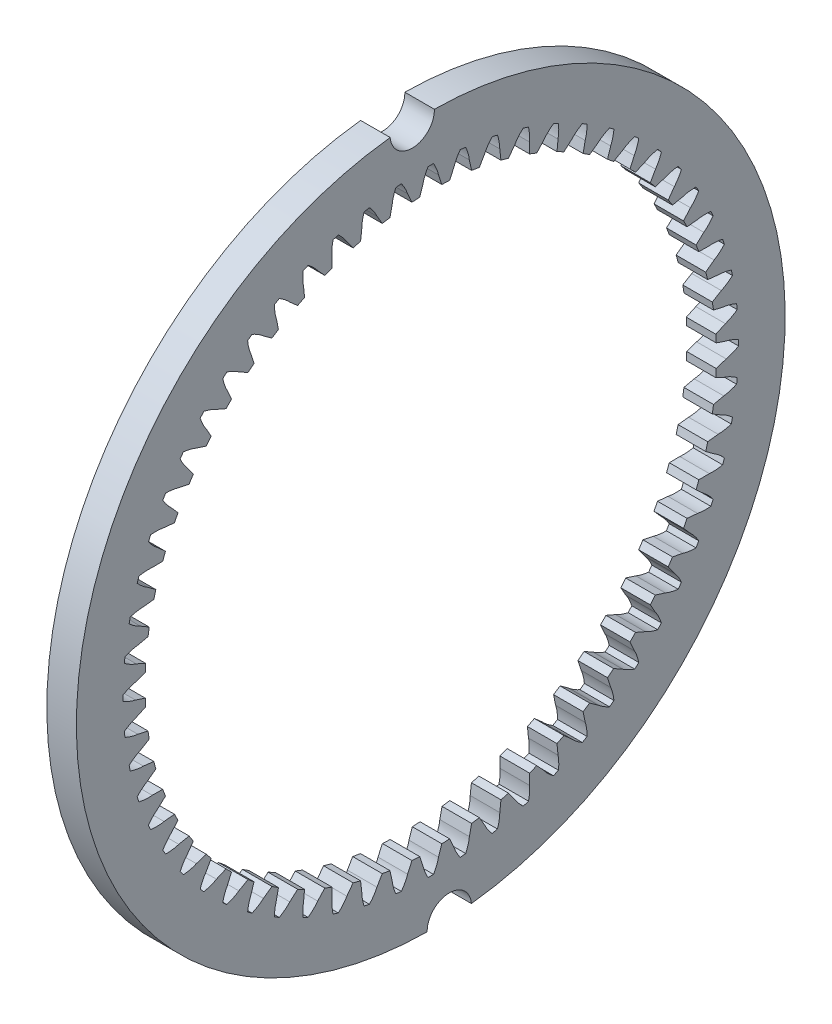
SolidWorks part; units mm, degrees
ref_plane "Front Plane" through (0, 0, 0) normal (0, 0, 1) x (1, 0, 0)
ref_plane "Top Plane" through (0, 0, 0) normal (0, 1, 0) x (1, 0, 0)
ref_plane "Right Plane" through (0, 0, 0) normal (1, 0, 0) x (0, 0, -1)
ref_plane "Plane1" through (1.5875, 0, 0) normal (1, 0, 0) x (0, 0, -1)
sketch "Sketch1" plane through (1.5875, 0, 0) normal (1, 0, 0) x (0, 0, -1)
  line L0 (4.1442, 31.4784) -> (4.3886, 30.3763)
  line L1 (5.2129, 30.2457) -> (5.786, 31.2183)
  line L2 (7.4119, 30.8727) -> (7.5398, 29.7511)
  line L3 (8.3459, 29.5351) -> (9.0175, 30.4425)
  line L4 (10.5984, 29.9289) -> (10.6083, 28.8)
  line L5 (11.3875, 28.5009) -> (12.1502, 29.3332)
  line L6 (13.6687, 28.6571) -> (13.5606, 27.5334)
  line L7 (14.3042, 27.1545) -> (15.1498, 27.9024)
  line L8 (16.5893, 27.0713) -> (16.3644, 25.9651)
  line L9 (17.0643, 25.5105) -> (17.9834, 26.166)
  line L10 (19.3282, 25.189) -> (18.9888, 24.1123)
  line L11 (19.6374, 23.5871) -> (20.62, 24.1429)
  line L12 (21.8553, 23.0306) -> (21.4052, 21.9953)
  line L13 (21.9953, 21.4052) -> (23.0306, 21.8553)
  line L14 (24.1429, 20.62) -> (23.5871, 19.6374)
  line L15 (24.1123, 18.9888) -> (25.189, 19.3282)
  line L16 (26.166, 17.9834) -> (25.5105, 17.0643)
  line L17 (25.9651, 16.3644) -> (27.0713, 16.5893)
  line L18 (27.9024, 15.1498) -> (27.1545, 14.3042)
  line L19 (27.5334, 13.5606) -> (28.6571, 13.6687)
  line L20 (29.3332, 12.1502) -> (28.5009, 11.3875)
  line L21 (28.8, 10.6083) -> (29.9289, 10.5984)
  line L22 (30.4425, 9.0175) -> (29.5351, 8.3459)
  line L23 (29.7511, 7.5398) -> (30.8727, 7.4119)
  line L24 (31.2183, 5.786) -> (30.2457, 5.2129)
  line L25 (30.3763, 4.3886) -> (31.4784, 4.1442)
  line L26 (31.6521, 2.4911) -> (30.6249, 2.0228)
  line L27 (30.6686, 1.1894) -> (31.7391, 0.8311)
  line L28 (31.7391, -0.8311) -> (30.6686, -1.1894)
  line L29 (30.6249, -2.0228) -> (31.6521, -2.4911)
  line L30 (31.4784, -4.1442) -> (30.3763, -4.3886)
  line L31 (30.2457, -5.2129) -> (31.2183, -5.786)
  line L32 (30.8727, -7.4119) -> (29.7511, -7.5398)
  line L33 (29.5351, -8.3459) -> (30.4425, -9.0175)
  line L34 (29.9289, -10.5984) -> (28.8, -10.6083)
  line L35 (28.5009, -11.3875) -> (29.3332, -12.1502)
  line L36 (28.6571, -13.6687) -> (27.5334, -13.5606)
  line L37 (27.1545, -14.3042) -> (27.9024, -15.1498)
  line L38 (27.0713, -16.5893) -> (25.9651, -16.3644)
  line L39 (25.5105, -17.0643) -> (26.166, -17.9834)
  line L40 (25.189, -19.3282) -> (24.1123, -18.9888)
  line L41 (23.5871, -19.6374) -> (24.1429, -20.62)
  line L42 (23.0306, -21.8553) -> (21.9953, -21.4052)
  line L43 (21.4052, -21.9953) -> (21.8553, -23.0306)
  line L44 (20.62, -24.1429) -> (19.6374, -23.5871)
  line L45 (18.9888, -24.1123) -> (19.3282, -25.189)
  line L46 (17.9834, -26.166) -> (17.0643, -25.5105)
  line L47 (16.3644, -25.9651) -> (16.5893, -27.0713)
  line L48 (15.1498, -27.9024) -> (14.3042, -27.1545)
  line L49 (13.5606, -27.5334) -> (13.6687, -28.6571)
  line L50 (12.1502, -29.3332) -> (11.3875, -28.5009)
  line L51 (10.6083, -28.8) -> (10.5984, -29.9289)
  line L52 (9.0175, -30.4425) -> (8.3459, -29.5351)
  line L53 (7.5398, -29.7511) -> (7.4119, -30.8727)
  line L54 (5.786, -31.2183) -> (5.2129, -30.2457)
  line L55 (4.3886, -30.3763) -> (4.1442, -31.4784)
  line L56 (2.4911, -31.6521) -> (2.0228, -30.6249)
  line L57 (1.1894, -30.6686) -> (0.8311, -31.7391)
  line L58 (-0.8311, -31.7391) -> (-1.1894, -30.6686)
  line L59 (-2.0228, -30.6249) -> (-2.4911, -31.6521)
  line L60 (-4.1442, -31.4784) -> (-4.3886, -30.3763)
  line L61 (-5.2129, -30.2457) -> (-5.786, -31.2183)
  line L62 (-7.4119, -30.8727) -> (-7.5398, -29.7511)
  line L63 (-8.3459, -29.5351) -> (-9.0175, -30.4425)
  line L64 (-10.5984, -29.9289) -> (-10.6083, -28.8)
  line L65 (-11.3875, -28.5009) -> (-12.1502, -29.3332)
  line L66 (-13.6687, -28.6571) -> (-13.5606, -27.5334)
  line L67 (-14.3042, -27.1545) -> (-15.1498, -27.9024)
  line L68 (-16.5893, -27.0713) -> (-16.3644, -25.9651)
  line L69 (-17.0643, -25.5105) -> (-17.9834, -26.166)
  line L70 (-19.3282, -25.189) -> (-18.9888, -24.1123)
  line L71 (-19.6374, -23.5871) -> (-20.62, -24.1429)
  line L72 (-21.8553, -23.0306) -> (-21.4052, -21.9953)
  line L73 (-21.9953, -21.4052) -> (-23.0306, -21.8553)
  line L74 (-24.1429, -20.62) -> (-23.5871, -19.6374)
  line L75 (-24.1123, -18.9888) -> (-25.189, -19.3282)
  line L76 (-26.166, -17.9834) -> (-25.5105, -17.0643)
  line L77 (-25.9651, -16.3644) -> (-27.0713, -16.5893)
  line L78 (-27.9024, -15.1498) -> (-27.1545, -14.3042)
  line L79 (-27.5334, -13.5606) -> (-28.6571, -13.6687)
  line L80 (-29.3332, -12.1502) -> (-28.5009, -11.3875)
  line L81 (-28.8, -10.6083) -> (-29.9289, -10.5984)
  line L82 (-30.4425, -9.0175) -> (-29.5351, -8.3459)
  line L83 (-29.7511, -7.5398) -> (-30.8727, -7.4119)
  line L84 (-31.2183, -5.786) -> (-30.2457, -5.2129)
  line L85 (-30.3763, -4.3886) -> (-31.4784, -4.1442)
  line L86 (-31.6521, -2.4911) -> (-30.6249, -2.0228)
  line L87 (-30.6686, -1.1894) -> (-31.7391, -0.8311)
  line L88 (-31.7391, 0.8311) -> (-30.6686, 1.1894)
  line L89 (-30.6249, 2.0228) -> (-31.6521, 2.4911)
  line L90 (-31.4784, 4.1442) -> (-30.3763, 4.3886)
  line L91 (-30.2457, 5.2129) -> (-31.2183, 5.786)
  line L92 (-30.8727, 7.4119) -> (-29.7511, 7.5398)
  line L93 (-29.5351, 8.3459) -> (-30.4425, 9.0175)
  line L94 (-29.9289, 10.5984) -> (-28.8, 10.6083)
  line L95 (-28.5009, 11.3875) -> (-29.3332, 12.1502)
  line L96 (-28.6571, 13.6687) -> (-27.5334, 13.5606)
  line L97 (-27.1545, 14.3042) -> (-27.9024, 15.1498)
  line L98 (-27.0713, 16.5893) -> (-25.9651, 16.3644)
  line L99 (-25.5105, 17.0643) -> (-26.166, 17.9834)
  line L100 (-25.189, 19.3282) -> (-24.1123, 18.9888)
  line L101 (-23.5871, 19.6374) -> (-24.1429, 20.62)
  line L102 (-23.0306, 21.8553) -> (-21.9953, 21.4052)
  line L103 (-21.4052, 21.9953) -> (-21.8553, 23.0306)
  line L104 (-20.62, 24.1429) -> (-19.6374, 23.5871)
  line L105 (-18.9888, 24.1123) -> (-19.3282, 25.189)
  line L106 (-17.9834, 26.166) -> (-17.0643, 25.5105)
  line L107 (-16.3644, 25.9651) -> (-16.5893, 27.0713)
  line L108 (-15.1498, 27.9024) -> (-14.3042, 27.1545)
  line L109 (-13.5606, 27.5334) -> (-13.6687, 28.6571)
  line L110 (-12.1502, 29.3332) -> (-11.3875, 28.5009)
  line L111 (-10.6083, 28.8) -> (-10.5984, 29.9289)
  line L112 (-9.0175, 30.4425) -> (-8.3459, 29.5351)
  line L113 (-7.5398, 29.7511) -> (-7.4119, 30.8727)
  line L114 (-5.786, 31.2183) -> (-5.2129, 30.2457)
  line L115 (-4.3886, 30.3763) -> (-4.1442, 31.4784)
  line L116 (-2.4911, 31.6521) -> (-2.0228, 30.6249)
  line L117 (-1.1894, 30.6686) -> (-0.8311, 31.7391)
  line L118 (0.8311, 31.7391) -> (1.1894, 30.6686)
  line L119 (2.0228, 30.6249) -> (2.4911, 31.6521)
  arc A0 (3.1625, 32.9192) -> (3.7509, 32.8574) centre (0, 0) cw
  arc A1 (4.3886, 30.3763) -> (5.2129, 30.2457) centre (0, 0) cw
  arc A2 (6.5862, 32.4083) -> (7.1649, 32.2853) centre (0, 0) cw
  arc A3 (7.5398, 29.7511) -> (8.3459, 29.5351) centre (0, 0) cw
  arc A4 (9.9377, 31.5423) -> (10.5003, 31.3595) centre (0, 0) cw
  arc A5 (10.6083, 28.8) -> (11.3875, 28.5009) centre (0, 0) cw
  arc A6 (13.1804, 30.3308) -> (13.7208, 30.0902) centre (0, 0) cw
  arc A7 (13.5606, 27.5334) -> (14.3042, 27.1545) centre (0, 0) cw
  arc A8 (16.2786, 28.7869) -> (16.7909, 28.4911) centre (0, 0) cw
  arc A9 (16.3644, 25.9651) -> (17.0643, 25.5105) centre (0, 0) cw
  arc A10 (19.1985, 26.9276) -> (19.677, 26.5799) centre (0, 0) cw
  arc A11 (18.9888, 24.1123) -> (19.6374, 23.5871) centre (0, 0) cw
  arc A12 (21.908, 24.7733) -> (22.3476, 24.3775) centre (0, 0) cw
  arc A13 (21.4052, 21.9953) -> (21.9953, 21.4052) centre (0, 0) cw
  arc A14 (24.3775, 22.3476) -> (24.7733, 21.908) centre (0, 0) cw
  arc A15 (23.5871, 19.6374) -> (24.1123, 18.9888) centre (0, 0) cw
  arc A16 (26.5799, 19.677) -> (26.9276, 19.1985) centre (0, 0) cw
  arc A17 (25.5105, 17.0643) -> (25.9651, 16.3644) centre (0, 0) cw
  arc A18 (28.4911, 16.7909) -> (28.7869, 16.2786) centre (0, 0) cw
  arc A19 (27.1545, 14.3042) -> (27.5334, 13.5606) centre (0, 0) cw
  arc A20 (30.0902, 13.7208) -> (30.3308, 13.1804) centre (0, 0) cw
  arc A21 (28.5009, 11.3875) -> (28.8, 10.6083) centre (0, 0) cw
  arc A22 (31.3595, 10.5003) -> (31.5423, 9.9377) centre (0, 0) cw
  arc A23 (29.5351, 8.3459) -> (29.7511, 7.5398) centre (0, 0) cw
  arc A24 (32.2853, 7.1649) -> (32.4083, 6.5862) centre (0, 0) cw
  arc A25 (30.2457, 5.2129) -> (30.3763, 4.3886) centre (0, 0) cw
  arc A26 (32.8574, 3.7509) -> (32.9192, 3.1625) centre (0, 0) cw
  arc A27 (30.6249, 2.0228) -> (30.6686, 1.1894) centre (0, 0) cw
  arc A28 (33.0695, 0.2958) -> (33.0695, -0.2958) centre (0, 0) cw
  arc A29 (30.6686, -1.1894) -> (30.6249, -2.0228) centre (0, 0) cw
  arc A30 (32.9192, -3.1625) -> (32.8574, -3.7509) centre (0, 0) cw
  arc A31 (30.3763, -4.3886) -> (30.2457, -5.2129) centre (0, 0) cw
  arc A32 (32.4083, -6.5862) -> (32.2853, -7.1649) centre (0, 0) cw
  arc A33 (29.7511, -7.5398) -> (29.5351, -8.3459) centre (0, 0) cw
  arc A34 (31.5423, -9.9377) -> (31.3595, -10.5003) centre (0, 0) cw
  arc A35 (28.8, -10.6083) -> (28.5009, -11.3875) centre (0, 0) cw
  arc A36 (30.3308, -13.1804) -> (30.0902, -13.7208) centre (0, 0) cw
  arc A37 (27.5334, -13.5606) -> (27.1545, -14.3042) centre (0, 0) cw
  arc A38 (28.7869, -16.2786) -> (28.4911, -16.7909) centre (0, 0) cw
  arc A39 (25.9651, -16.3644) -> (25.5105, -17.0643) centre (0, 0) cw
  arc A40 (26.9276, -19.1985) -> (26.5799, -19.677) centre (0, 0) cw
  arc A41 (24.1123, -18.9888) -> (23.5871, -19.6374) centre (0, 0) cw
  arc A42 (24.7733, -21.908) -> (24.3775, -22.3476) centre (0, 0) cw
  arc A43 (21.9953, -21.4052) -> (21.4052, -21.9953) centre (0, 0) cw
  arc A44 (22.3476, -24.3775) -> (21.908, -24.7733) centre (0, 0) cw
  arc A45 (19.6374, -23.5871) -> (18.9888, -24.1123) centre (0, 0) cw
  arc A46 (19.677, -26.5799) -> (19.1985, -26.9276) centre (0, 0) cw
  arc A47 (17.0643, -25.5105) -> (16.3644, -25.9651) centre (0, 0) cw
  arc A48 (16.7909, -28.4911) -> (16.2786, -28.7869) centre (0, 0) cw
  arc A49 (14.3042, -27.1545) -> (13.5606, -27.5334) centre (0, 0) cw
  arc A50 (13.7208, -30.0902) -> (13.1804, -30.3308) centre (0, 0) cw
  arc A51 (11.3875, -28.5009) -> (10.6083, -28.8) centre (0, 0) cw
  arc A52 (10.5003, -31.3595) -> (9.9377, -31.5423) centre (0, 0) cw
  arc A53 (8.3459, -29.5351) -> (7.5398, -29.7511) centre (0, 0) cw
  arc A54 (7.1649, -32.2853) -> (6.5862, -32.4083) centre (0, 0) cw
  arc A55 (5.2129, -30.2457) -> (4.3886, -30.3763) centre (0, 0) cw
  arc A56 (3.7509, -32.8574) -> (3.1625, -32.9192) centre (0, 0) cw
  arc A57 (2.0228, -30.6249) -> (1.1894, -30.6686) centre (0, 0) cw
  arc A58 (0.2958, -33.0695) -> (-0.2958, -33.0695) centre (0, 0) cw
  arc A59 (-1.1894, -30.6686) -> (-2.0228, -30.6249) centre (0, 0) cw
  arc A60 (-3.1625, -32.9192) -> (-3.7509, -32.8574) centre (0, 0) cw
  arc A61 (-4.3886, -30.3763) -> (-5.2129, -30.2457) centre (0, 0) cw
  arc A62 (-6.5862, -32.4083) -> (-7.1649, -32.2853) centre (0, 0) cw
  arc A63 (-7.5398, -29.7511) -> (-8.3459, -29.5351) centre (0, 0) cw
  arc A64 (-9.9377, -31.5423) -> (-10.5003, -31.3595) centre (0, 0) cw
  arc A65 (-10.6083, -28.8) -> (-11.3875, -28.5009) centre (0, 0) cw
  arc A66 (-13.1804, -30.3308) -> (-13.7208, -30.0902) centre (0, 0) cw
  arc A67 (-13.5606, -27.5334) -> (-14.3042, -27.1545) centre (0, 0) cw
  arc A68 (-16.2786, -28.7869) -> (-16.7909, -28.4911) centre (0, 0) cw
  arc A69 (-16.3644, -25.9651) -> (-17.0643, -25.5105) centre (0, 0) cw
  arc A70 (-19.1985, -26.9276) -> (-19.677, -26.5799) centre (0, 0) cw
  arc A71 (-18.9888, -24.1123) -> (-19.6374, -23.5871) centre (0, 0) cw
  arc A72 (-21.908, -24.7733) -> (-22.3476, -24.3775) centre (0, 0) cw
  arc A73 (-21.4052, -21.9953) -> (-21.9953, -21.4052) centre (0, 0) cw
  arc A74 (-24.3775, -22.3476) -> (-24.7733, -21.908) centre (0, 0) cw
  arc A75 (-23.5871, -19.6374) -> (-24.1123, -18.9888) centre (0, 0) cw
  arc A76 (-26.5799, -19.677) -> (-26.9276, -19.1985) centre (0, 0) cw
  arc A77 (-25.5105, -17.0643) -> (-25.9651, -16.3644) centre (0, 0) cw
  arc A78 (-28.4911, -16.7909) -> (-28.7869, -16.2786) centre (0, 0) cw
  arc A79 (-27.1545, -14.3042) -> (-27.5334, -13.5606) centre (0, 0) cw
  arc A80 (-30.0902, -13.7208) -> (-30.3308, -13.1804) centre (0, 0) cw
  arc A81 (-28.5009, -11.3875) -> (-28.8, -10.6083) centre (0, 0) cw
  arc A82 (-31.3595, -10.5003) -> (-31.5423, -9.9377) centre (0, 0) cw
  arc A83 (-29.5351, -8.3459) -> (-29.7511, -7.5398) centre (0, 0) cw
  arc A84 (-32.2853, -7.1649) -> (-32.4083, -6.5862) centre (0, 0) cw
  arc A85 (-30.2457, -5.2129) -> (-30.3763, -4.3886) centre (0, 0) cw
  arc A86 (-32.8574, -3.7509) -> (-32.9192, -3.1625) centre (0, 0) cw
  arc A87 (-30.6249, -2.0228) -> (-30.6686, -1.1894) centre (0, 0) cw
  arc A88 (-33.0695, -0.2958) -> (-33.0695, 0.2958) centre (0, 0) cw
  arc A89 (-30.6686, 1.1894) -> (-30.6249, 2.0228) centre (0, 0) cw
  arc A90 (-32.9192, 3.1625) -> (-32.8574, 3.7509) centre (0, 0) cw
  arc A91 (-30.3763, 4.3886) -> (-30.2457, 5.2129) centre (0, 0) cw
  arc A92 (-32.4083, 6.5862) -> (-32.2853, 7.1649) centre (0, 0) cw
  arc A93 (-29.7511, 7.5398) -> (-29.5351, 8.3459) centre (0, 0) cw
  arc A94 (-31.5423, 9.9377) -> (-31.3595, 10.5003) centre (0, 0) cw
  arc A95 (-28.8, 10.6083) -> (-28.5009, 11.3875) centre (0, 0) cw
  arc A96 (-30.3308, 13.1804) -> (-30.0902, 13.7208) centre (0, 0) cw
  arc A97 (-27.5334, 13.5606) -> (-27.1545, 14.3042) centre (0, 0) cw
  arc A98 (-28.7869, 16.2786) -> (-28.4911, 16.7909) centre (0, 0) cw
  arc A99 (-25.9651, 16.3644) -> (-25.5105, 17.0643) centre (0, 0) cw
  arc A100 (-26.9276, 19.1985) -> (-26.5799, 19.677) centre (0, 0) cw
  arc A101 (-24.1123, 18.9888) -> (-23.5871, 19.6374) centre (0, 0) cw
  arc A102 (-24.7733, 21.908) -> (-24.3775, 22.3476) centre (0, 0) cw
  arc A103 (-21.9953, 21.4052) -> (-21.4052, 21.9953) centre (0, 0) cw
  arc A104 (-22.3476, 24.3775) -> (-21.908, 24.7733) centre (0, 0) cw
  arc A105 (-19.6374, 23.5871) -> (-18.9888, 24.1123) centre (0, 0) cw
  arc A106 (-19.677, 26.5799) -> (-19.1985, 26.9276) centre (0, 0) cw
  arc A107 (-17.0643, 25.5105) -> (-16.3644, 25.9651) centre (0, 0) cw
  arc A108 (-16.7909, 28.4911) -> (-16.2786, 28.7869) centre (0, 0) cw
  arc A109 (-14.3042, 27.1545) -> (-13.5606, 27.5334) centre (0, 0) cw
  arc A110 (-13.7208, 30.0902) -> (-13.1804, 30.3308) centre (0, 0) cw
  arc A111 (-11.3875, 28.5009) -> (-10.6083, 28.8) centre (0, 0) cw
  arc A112 (-10.5003, 31.3595) -> (-9.9377, 31.5423) centre (0, 0) cw
  arc A113 (-8.3459, 29.5351) -> (-7.5398, 29.7511) centre (0, 0) cw
  arc A114 (-7.1649, 32.2853) -> (-6.5862, 32.4083) centre (0, 0) cw
  arc A115 (-5.2129, 30.2457) -> (-4.3886, 30.3763) centre (0, 0) cw
  arc A116 (-3.7509, 32.8574) -> (-3.1625, 32.9192) centre (0, 0) cw
  arc A117 (-2.0228, 30.6249) -> (-1.1894, 30.6686) centre (0, 0) cw
  arc A118 (-0.2958, 33.0695) -> (0.2958, 33.0695) centre (0, 0) cw
  arc A119 (1.1894, 30.6686) -> (2.0228, 30.6249) centre (0, 0) cw
  circle A120 centre (0, 0) radius 38.0746
  spline S0 degree 3 poles (2.4911, 31.6521) (2.5346, 31.7951) (2.5901, 31.9347) (2.6528, 32.0704) (2.7217, 32.2196) (2.8, 32.3646) (2.885, 32.5053) (2.9709, 32.6475) (3.064, 32.7855) (3.1625, 32.9192) knots 0 0 0 0 0.000448 0.000448 0.000448 0.000941 0.000941 0.000941 0.001439 0.001439 0.001439 0.001439
  spline S1 degree 3 poles (3.7509, 32.8574) (3.8086, 32.7255) (3.8619, 32.5916) (3.9099, 32.4559) (3.9579, 32.3202) (4.0007, 32.1825) (4.0371, 32.0432) (4.0856, 31.8578) (4.1233, 31.6689) (4.1442, 31.4784) knots 0 0 0 0 0.000432 0.000432 0.000432 0.000864 0.000864 0.000864 0.00144 0.00144 0.00144 0.00144
  spline S2 degree 3 poles (5.786, 31.2183) (5.8442, 31.356) (5.914, 31.489) (5.9905, 31.6174) (6.0747, 31.7586) (6.1677, 31.8947) (6.2669, 32.0256) (6.3673, 32.1581) (6.4742, 32.2856) (6.5862, 32.4083) knots 0 0 0 0 0.000448 0.000448 0.000448 0.000941 0.000941 0.000941 0.001439 0.001439 0.001439 0.001439
  spline S3 degree 3 poles (7.1649, 32.2853) (7.2085, 32.1482) (7.2475, 32.0094) (7.281, 31.8694) (7.3145, 31.7294) (7.3427, 31.588) (7.3644, 31.4457) (7.3933, 31.2562) (7.411, 31.0644) (7.4119, 30.8727) knots 0 0 0 0 0.000432 0.000432 0.000432 0.000864 0.000864 0.000864 0.00144 0.00144 0.00144 0.00144
  spline S4 degree 3 poles (9.0175, 30.4425) (9.0898, 30.5734) (9.1731, 30.6983) (9.2626, 30.818) (9.3611, 30.9496) (9.4678, 31.0752) (9.5802, 31.1951) (9.6938, 31.3163) (9.8135, 31.432) (9.9377, 31.5423) knots 0 0 0 0 0.000448 0.000448 0.000448 0.000941 0.000941 0.000941 0.001439 0.001439 0.001439 0.001439
  spline S5 degree 3 poles (10.5003, 31.3595) (10.5294, 31.2186) (10.5537, 31.0765) (10.5724, 30.9338) (10.5911, 30.791) (10.6044, 30.6474) (10.6111, 30.5036) (10.62, 30.3122) (10.6175, 30.1195) (10.5984, 29.9289) knots 0 0 0 0 0.000432 0.000432 0.000432 0.000864 0.000864 0.000864 0.00144 0.00144 0.00144 0.00144
  spline S6 degree 3 poles (12.1502, 29.3332) (12.2358, 29.4557) (12.3317, 29.5713) (12.4333, 29.681) (12.5449, 29.8016) (12.6642, 29.9153) (12.7885, 30.0228) (12.9142, 30.1315) (13.0453, 30.2341) (13.1804, 30.3308) knots 0 0 0 0 0.000448 0.000448 0.000448 0.000941 0.000941 0.000941 0.001439 0.001439 0.001439 0.001439
  spline S7 degree 3 poles (13.7208, 30.0902) (13.7349, 29.9469) (13.7442, 29.8031) (13.7479, 29.6592) (13.7516, 29.5153) (13.7498, 29.3711) (13.7414, 29.2274) (13.7303, 29.0361) (13.7077, 28.8447) (13.6687, 28.6571) knots 0 0 0 0 0.000432 0.000432 0.000432 0.000864 0.000864 0.000864 0.00144 0.00144 0.00144 0.00144
  spline S8 degree 3 poles (15.1498, 27.9024) (15.2477, 28.0154) (15.3552, 28.1203) (15.4677, 28.2188) (15.5913, 28.327) (15.7218, 28.4277) (15.8567, 28.5216) (15.993, 28.6165) (16.1342, 28.7048) (16.2786, 28.7869) knots 0 0 0 0 0.000448 0.000448 0.000448 0.000941 0.000941 0.000941 0.001439 0.001439 0.001439 0.001439
  spline S9 degree 3 poles (16.7909, 28.4911) (16.79, 28.3472) (16.7842, 28.2032) (16.7728, 28.0597) (16.7615, 27.9162) (16.7446, 27.7729) (16.7212, 27.6309) (16.6902, 27.4418) (16.6477, 27.2539) (16.5893, 27.0713) knots 0 0 0 0 0.000432 0.000432 0.000432 0.000864 0.000864 0.000864 0.00144 0.00144 0.00144 0.00144
  spline S10 degree 3 poles (17.9834, 26.166) (18.0926, 26.2681) (18.2104, 26.3612) (18.3326, 26.4474) (18.4669, 26.5421) (18.6072, 26.6286) (18.7511, 26.7079) (18.8966, 26.7881) (19.0462, 26.8611) (19.1985, 26.9276) knots 0 0 0 0 0.000448 0.000448 0.000448 0.000941 0.000941 0.000941 0.001439 0.001439 0.001439 0.001439
  spline S11 degree 3 poles (19.677, 26.5799) (19.6611, 26.4369) (19.6403, 26.2942) (19.614, 26.1527) (19.5877, 26.0112) (19.5559, 25.8705) (19.5178, 25.7317) (19.4672, 25.5469) (19.4053, 25.3644) (19.3282, 25.189) knots 0 0 0 0 0.000432 0.000432 0.000432 0.000864 0.000864 0.000864 0.00144 0.00144 0.00144 0.00144
  spline S12 degree 3 poles (20.62, 24.1429) (20.7392, 24.233) (20.8662, 24.3133) (20.9967, 24.3862) (21.1401, 24.4664) (21.2887, 24.5377) (21.4402, 24.6015) (21.5932, 24.6661) (21.7496, 24.7231) (21.908, 24.7733) knots 0 0 0 0 0.000448 0.000448 0.000448 0.000941 0.000941 0.000941 0.001439 0.001439 0.001439 0.001439
  spline S13 degree 3 poles (22.3476, 24.3775) (22.3168, 24.2369) (22.2812, 24.0972) (22.2403, 23.9592) (22.1993, 23.8212) (22.153, 23.6846) (22.1006, 23.5505) (22.0309, 23.372) (21.9503, 23.1971) (21.8553, 23.0306) knots 0 0 0 0 0.000432 0.000432 0.000432 0.000864 0.000864 0.000864 0.00144 0.00144 0.00144 0.00144
  spline S14 degree 3 poles (23.0306, 21.8553) (23.1587, 21.9324) (23.2933, 21.999) (23.4307, 22.0579) (23.5817, 22.1226) (23.737, 22.178) (23.8943, 22.2257) (24.0533, 22.2738) (24.2148, 22.3142) (24.3775, 22.3476) knots 0 0 0 0 0.000448 0.000448 0.000448 0.000941 0.000941 0.000941 0.001439 0.001439 0.001439 0.001439
  spline S15 degree 3 poles (24.7733, 21.908) (24.728, 21.7714) (24.678, 21.6362) (24.6228, 21.5032) (24.5677, 21.3703) (24.5074, 21.2393) (24.4412, 21.1114) (24.3533, 20.9411) (24.2548, 20.7756) (24.1429, 20.62) knots 0 0 0 0 0.000432 0.000432 0.000432 0.000864 0.000864 0.000864 0.00144 0.00144 0.00144 0.00144
  spline S16 degree 3 poles (25.189, 19.3282) (25.3244, 19.3915) (25.4652, 19.4437) (25.608, 19.4879) (25.765, 19.5365) (25.9252, 19.5753) (26.0866, 19.6063) (26.2497, 19.6376) (26.4146, 19.6608) (26.5799, 19.677) knots 0 0 0 0 0.000448 0.000448 0.000448 0.000941 0.000941 0.000941 0.001439 0.001439 0.001439 0.001439
  spline S17 degree 3 poles (26.9276, 19.1985) (26.8683, 19.0673) (26.8044, 18.9381) (26.7357, 18.8117) (26.6669, 18.6852) (26.5932, 18.5612) (26.5141, 18.4409) (26.4088, 18.2808) (26.2935, 18.1264) (26.166, 17.9834) knots 0 0 0 0 0.000432 0.000432 0.000432 0.000864 0.000864 0.000864 0.00144 0.00144 0.00144 0.00144
  spline S18 degree 3 poles (27.0713, 16.5893) (27.2126, 16.6382) (27.3581, 16.6753) (27.5048, 16.7044) (27.666, 16.7363) (27.8294, 16.7582) (27.9931, 16.7721) (28.1586, 16.7862) (28.325, 16.792) (28.4911, 16.7909) knots 0 0 0 0 0.000448 0.000448 0.000448 0.000941 0.000941 0.000941 0.001439 0.001439 0.001439 0.001439
  spline S19 degree 3 poles (28.7869, 16.2786) (28.7142, 16.1544) (28.6371, 16.0326) (28.5556, 15.914) (28.474, 15.7954) (28.3877, 15.6798) (28.2965, 15.5684) (28.175, 15.4202) (28.0442, 15.2787) (27.9024, 15.1498) knots 0 0 0 0 0.000432 0.000432 0.000432 0.000864 0.000864 0.000864 0.00144 0.00144 0.00144 0.00144
  spline S20 degree 3 poles (28.6571, 13.6687) (28.8027, 13.7025) (28.9513, 13.7243) (29.1002, 13.7378) (29.2638, 13.7527) (29.4286, 13.7574) (29.5929, 13.7541) (29.759, 13.7508) (29.9251, 13.7393) (30.0902, 13.7208) knots 0 0 0 0 0.000448 0.000448 0.000448 0.000941 0.000941 0.000941 0.001439 0.001439 0.001439 0.001439
  spline S21 degree 3 poles (30.3308, 13.1804) (30.2454, 13.0644) (30.1561, 12.9513) (30.0626, 12.8419) (29.969, 12.7325) (29.8712, 12.6266) (29.7688, 12.5254) (29.6325, 12.3906) (29.4877, 12.2636) (29.3332, 12.1502) knots 0 0 0 0 0.000432 0.000432 0.000432 0.000864 0.000864 0.000864 0.00144 0.00144 0.00144 0.00144
  spline S22 degree 3 poles (29.9289, 10.5984) (30.0772, 10.6168) (30.2273, 10.6228) (30.3768, 10.6208) (30.5411, 10.6185) (30.7054, 10.6059) (30.8685, 10.5855) (31.0333, 10.5648) (31.1973, 10.536) (31.3595, 10.5003) knots 0 0 0 0 0.000448 0.000448 0.000448 0.000941 0.000941 0.000941 0.001439 0.001439 0.001439 0.001439
  spline S23 degree 3 poles (31.5423, 9.9377) (31.4454, 9.8314) (31.3447, 9.7282) (31.2402, 9.6292) (31.1358, 9.5301) (31.0274, 9.435) (30.915, 9.3451) (30.7653, 9.2253) (30.608, 9.1141) (30.4425, 9.0175) knots 0 0 0 0 0.000432 0.000432 0.000432 0.000864 0.000864 0.000864 0.00144 0.00144 0.00144 0.00144
  spline S24 degree 3 poles (30.8727, 7.4119) (31.0222, 7.4147) (31.1721, 7.405) (31.3205, 7.3873) (31.4837, 7.3679) (31.6458, 7.3382) (31.8059, 7.3009) (31.9677, 7.2631) (32.1277, 7.2173) (32.2853, 7.1649) knots 0 0 0 0 0.000448 0.000448 0.000448 0.000941 0.000941 0.000941 0.001439 0.001439 0.001439 0.001439
  spline S25 degree 3 poles (32.4083, 6.5862) (32.3008, 6.4906) (32.1899, 6.3985) (32.0756, 6.3109) (31.9614, 6.2233) (31.8436, 6.1401) (31.7224, 6.0624) (31.5611, 5.9589) (31.393, 5.8648) (31.2183, 5.786) knots 0 0 0 0 0.000432 0.000432 0.000432 0.000864 0.000864 0.000864 0.00144 0.00144 0.00144 0.00144
  spline S26 degree 3 poles (31.4784, 4.1442) (31.6273, 4.1314) (31.7754, 4.1061) (31.9211, 4.073) (32.0814, 4.0366) (32.2395, 3.9901) (32.3948, 3.9362) (32.5517, 3.8818) (32.7061, 3.8195) (32.8574, 3.7509) knots 0 0 0 0 0.000448 0.000448 0.000448 0.000941 0.000941 0.000941 0.001439 0.001439 0.001439 0.001439
  spline S27 degree 3 poles (32.9192, 3.1625) (32.8023, 3.0787) (32.6824, 2.9987) (32.5596, 2.9235) (32.4368, 2.8484) (32.311, 2.7779) (32.1823, 2.7133) (32.0111, 2.6273) (31.8341, 2.5512) (31.6521, 2.4911) knots 0 0 0 0 0.000432 0.000432 0.000432 0.000864 0.000864 0.000864 0.00144 0.00144 0.00144 0.00144
  spline S28 degree 3 poles (31.7391, 0.8311) (31.8859, 0.8028) (32.0305, 0.7622) (32.172, 0.714) (32.3276, 0.6611) (32.48, 0.5983) (32.6288, 0.5285) (32.7792, 0.4579) (32.9262, 0.3798) (33.0695, 0.2958) knots 0 0 0 0 0.000448 0.000448 0.000448 0.000941 0.000941 0.000941 0.001439 0.001439 0.001439 0.001439
  spline S29 degree 3 poles (33.0695, -0.2958) (32.9444, -0.367) (32.8168, -0.434) (32.6868, -0.4959) (32.5568, -0.5578) (32.4244, -0.6148) (32.2897, -0.6656) (32.1104, -0.7332) (31.9264, -0.7904) (31.7391, -0.8311) knots 0 0 0 0 0.000432 0.000432 0.000432 0.000864 0.000864 0.000864 0.00144 0.00144 0.00144 0.00144
  spline S30 degree 3 poles (31.6521, -2.4911) (31.7951, -2.5346) (31.9347, -2.5901) (32.0704, -2.6528) (32.2196, -2.7217) (32.3646, -2.8) (32.5053, -2.885) (32.6475, -2.9709) (32.7855, -3.064) (32.9192, -3.1625) knots 0 0 0 0 0.000448 0.000448 0.000448 0.000941 0.000941 0.000941 0.001439 0.001439 0.001439 0.001439
  spline S31 degree 3 poles (32.8574, -3.7509) (32.7255, -3.8086) (32.5916, -3.8619) (32.4559, -3.9099) (32.3202, -3.9579) (32.1825, -4.0007) (32.0432, -4.0371) (31.8578, -4.0856) (31.6689, -4.1233) (31.4784, -4.1442) knots 0 0 0 0 0.000432 0.000432 0.000432 0.000864 0.000864 0.000864 0.00144 0.00144 0.00144 0.00144
  spline S32 degree 3 poles (31.2183, -5.786) (31.356, -5.8442) (31.489, -5.914) (31.6174, -5.9905) (31.7586, -6.0747) (31.8947, -6.1677) (32.0256, -6.2669) (32.1581, -6.3673) (32.2856, -6.4742) (32.4083, -6.5862) knots 0 0 0 0 0.000448 0.000448 0.000448 0.000941 0.000941 0.000941 0.001439 0.001439 0.001439 0.001439
  spline S33 degree 3 poles (32.2853, -7.1649) (32.1482, -7.2085) (32.0094, -7.2475) (31.8694, -7.281) (31.7294, -7.3145) (31.588, -7.3427) (31.4457, -7.3644) (31.2562, -7.3933) (31.0644, -7.411) (30.8727, -7.4119) knots 0 0 0 0 0.000432 0.000432 0.000432 0.000864 0.000864 0.000864 0.00144 0.00144 0.00144 0.00144
  spline S34 degree 3 poles (30.4425, -9.0175) (30.5734, -9.0898) (30.6983, -9.1731) (30.818, -9.2626) (30.9496, -9.3611) (31.0752, -9.4678) (31.1951, -9.5802) (31.3163, -9.6938) (31.432, -9.8135) (31.5423, -9.9377) knots 0 0 0 0 0.000448 0.000448 0.000448 0.000941 0.000941 0.000941 0.001439 0.001439 0.001439 0.001439
  spline S35 degree 3 poles (31.3595, -10.5003) (31.2186, -10.5294) (31.0765, -10.5537) (30.9338, -10.5724) (30.791, -10.5911) (30.6474, -10.6044) (30.5036, -10.6111) (30.3122, -10.62) (30.1195, -10.6175) (29.9289, -10.5984) knots 0 0 0 0 0.000432 0.000432 0.000432 0.000864 0.000864 0.000864 0.00144 0.00144 0.00144 0.00144
  spline S36 degree 3 poles (29.3332, -12.1502) (29.4557, -12.2358) (29.5713, -12.3317) (29.681, -12.4333) (29.8016, -12.5449) (29.9153, -12.6642) (30.0228, -12.7885) (30.1315, -12.9142) (30.2341, -13.0453) (30.3308, -13.1804) knots 0 0 0 0 0.000448 0.000448 0.000448 0.000941 0.000941 0.000941 0.001439 0.001439 0.001439 0.001439
  spline S37 degree 3 poles (30.0902, -13.7208) (29.9469, -13.7349) (29.8031, -13.7442) (29.6592, -13.7479) (29.5153, -13.7516) (29.3711, -13.7498) (29.2274, -13.7414) (29.0361, -13.7303) (28.8447, -13.7077) (28.6571, -13.6687) knots 0 0 0 0 0.000432 0.000432 0.000432 0.000864 0.000864 0.000864 0.00144 0.00144 0.00144 0.00144
  spline S38 degree 3 poles (27.9024, -15.1498) (28.0154, -15.2477) (28.1203, -15.3552) (28.2188, -15.4677) (28.327, -15.5913) (28.4277, -15.7218) (28.5216, -15.8567) (28.6165, -15.993) (28.7048, -16.1342) (28.7869, -16.2786) knots 0 0 0 0 0.000448 0.000448 0.000448 0.000941 0.000941 0.000941 0.001439 0.001439 0.001439 0.001439
  spline S39 degree 3 poles (28.4911, -16.7909) (28.3472, -16.79) (28.2032, -16.7842) (28.0597, -16.7728) (27.9162, -16.7615) (27.7729, -16.7446) (27.6309, -16.7212) (27.4418, -16.6902) (27.2539, -16.6477) (27.0713, -16.5893) knots 0 0 0 0 0.000432 0.000432 0.000432 0.000864 0.000864 0.000864 0.00144 0.00144 0.00144 0.00144
  spline S40 degree 3 poles (26.166, -17.9834) (26.2681, -18.0926) (26.3612, -18.2104) (26.4474, -18.3326) (26.5421, -18.4669) (26.6286, -18.6072) (26.7079, -18.7511) (26.7881, -18.8966) (26.8611, -19.0462) (26.9276, -19.1985) knots 0 0 0 0 0.000448 0.000448 0.000448 0.000941 0.000941 0.000941 0.001439 0.001439 0.001439 0.001439
  spline S41 degree 3 poles (26.5799, -19.677) (26.4369, -19.6611) (26.2942, -19.6403) (26.1527, -19.614) (26.0112, -19.5877) (25.8705, -19.5559) (25.7317, -19.5178) (25.5469, -19.4672) (25.3644, -19.4053) (25.189, -19.3282) knots 0 0 0 0 0.000432 0.000432 0.000432 0.000864 0.000864 0.000864 0.00144 0.00144 0.00144 0.00144
  spline S42 degree 3 poles (24.1429, -20.62) (24.233, -20.7392) (24.3133, -20.8662) (24.3862, -20.9967) (24.4664, -21.1401) (24.5377, -21.2887) (24.6015, -21.4402) (24.6661, -21.5932) (24.7231, -21.7496) (24.7733, -21.908) knots 0 0 0 0 0.000448 0.000448 0.000448 0.000941 0.000941 0.000941 0.001439 0.001439 0.001439 0.001439
  spline S43 degree 3 poles (24.3775, -22.3476) (24.2369, -22.3168) (24.0972, -22.2812) (23.9592, -22.2403) (23.8212, -22.1993) (23.6846, -22.153) (23.5505, -22.1006) (23.372, -22.0309) (23.1971, -21.9503) (23.0306, -21.8553) knots 0 0 0 0 0.000432 0.000432 0.000432 0.000864 0.000864 0.000864 0.00144 0.00144 0.00144 0.00144
  spline S44 degree 3 poles (21.8553, -23.0306) (21.9324, -23.1587) (21.999, -23.2933) (22.0579, -23.4307) (22.1226, -23.5817) (22.178, -23.737) (22.2257, -23.8943) (22.2738, -24.0533) (22.3142, -24.2148) (22.3476, -24.3775) knots 0 0 0 0 0.000448 0.000448 0.000448 0.000941 0.000941 0.000941 0.001439 0.001439 0.001439 0.001439
  spline S45 degree 3 poles (21.908, -24.7733) (21.7714, -24.728) (21.6362, -24.678) (21.5032, -24.6228) (21.3703, -24.5677) (21.2393, -24.5074) (21.1114, -24.4412) (20.9411, -24.3533) (20.7756, -24.2548) (20.62, -24.1429) knots 0 0 0 0 0.000432 0.000432 0.000432 0.000864 0.000864 0.000864 0.00144 0.00144 0.00144 0.00144
  spline S46 degree 3 poles (19.3282, -25.189) (19.3915, -25.3244) (19.4437, -25.4652) (19.4879, -25.608) (19.5365, -25.765) (19.5753, -25.9252) (19.6063, -26.0866) (19.6376, -26.2497) (19.6608, -26.4146) (19.677, -26.5799) knots 0 0 0 0 0.000448 0.000448 0.000448 0.000941 0.000941 0.000941 0.001439 0.001439 0.001439 0.001439
  spline S47 degree 3 poles (19.1985, -26.9276) (19.0673, -26.8683) (18.9381, -26.8044) (18.8117, -26.7357) (18.6852, -26.6669) (18.5612, -26.5932) (18.4409, -26.5141) (18.2808, -26.4088) (18.1264, -26.2935) (17.9834, -26.166) knots 0 0 0 0 0.000432 0.000432 0.000432 0.000864 0.000864 0.000864 0.00144 0.00144 0.00144 0.00144
  spline S48 degree 3 poles (16.5893, -27.0713) (16.6382, -27.2126) (16.6753, -27.3581) (16.7044, -27.5048) (16.7363, -27.666) (16.7582, -27.8294) (16.7721, -27.9931) (16.7862, -28.1586) (16.792, -28.325) (16.7909, -28.4911) knots 0 0 0 0 0.000448 0.000448 0.000448 0.000941 0.000941 0.000941 0.001439 0.001439 0.001439 0.001439
  spline S49 degree 3 poles (16.2786, -28.7869) (16.1544, -28.7142) (16.0326, -28.6371) (15.914, -28.5556) (15.7954, -28.474) (15.6798, -28.3877) (15.5684, -28.2965) (15.4202, -28.175) (15.2787, -28.0442) (15.1498, -27.9024) knots 0 0 0 0 0.000432 0.000432 0.000432 0.000864 0.000864 0.000864 0.00144 0.00144 0.00144 0.00144
  spline S50 degree 3 poles (13.6687, -28.6571) (13.7025, -28.8027) (13.7243, -28.9513) (13.7378, -29.1002) (13.7527, -29.2638) (13.7574, -29.4286) (13.7541, -29.5929) (13.7508, -29.759) (13.7393, -29.9251) (13.7208, -30.0902) knots 0 0 0 0 0.000448 0.000448 0.000448 0.000941 0.000941 0.000941 0.001439 0.001439 0.001439 0.001439
  spline S51 degree 3 poles (13.1804, -30.3308) (13.0644, -30.2454) (12.9513, -30.1561) (12.8419, -30.0626) (12.7325, -29.969) (12.6266, -29.8712) (12.5254, -29.7688) (12.3906, -29.6325) (12.2636, -29.4877) (12.1502, -29.3332) knots 0 0 0 0 0.000432 0.000432 0.000432 0.000864 0.000864 0.000864 0.00144 0.00144 0.00144 0.00144
  spline S52 degree 3 poles (10.5984, -29.9289) (10.6168, -30.0772) (10.6228, -30.2273) (10.6208, -30.3768) (10.6185, -30.5411) (10.6059, -30.7054) (10.5855, -30.8685) (10.5648, -31.0333) (10.536, -31.1973) (10.5003, -31.3595) knots 0 0 0 0 0.000448 0.000448 0.000448 0.000941 0.000941 0.000941 0.001439 0.001439 0.001439 0.001439
  spline S53 degree 3 poles (9.9377, -31.5423) (9.8314, -31.4454) (9.7282, -31.3447) (9.6292, -31.2402) (9.5301, -31.1358) (9.435, -31.0274) (9.3451, -30.915) (9.2253, -30.7653) (9.1141, -30.608) (9.0175, -30.4425) knots 0 0 0 0 0.000432 0.000432 0.000432 0.000864 0.000864 0.000864 0.00144 0.00144 0.00144 0.00144
  spline S54 degree 3 poles (7.4119, -30.8727) (7.4147, -31.0222) (7.405, -31.1721) (7.3873, -31.3205) (7.3679, -31.4837) (7.3382, -31.6458) (7.3009, -31.8059) (7.2631, -31.9677) (7.2173, -32.1277) (7.1649, -32.2853) knots 0 0 0 0 0.000448 0.000448 0.000448 0.000941 0.000941 0.000941 0.001439 0.001439 0.001439 0.001439
  spline S55 degree 3 poles (6.5862, -32.4083) (6.4906, -32.3008) (6.3985, -32.1899) (6.3109, -32.0756) (6.2233, -31.9614) (6.1401, -31.8436) (6.0624, -31.7224) (5.9589, -31.5611) (5.8648, -31.393) (5.786, -31.2183) knots 0 0 0 0 0.000432 0.000432 0.000432 0.000864 0.000864 0.000864 0.00144 0.00144 0.00144 0.00144
  spline S56 degree 3 poles (4.1442, -31.4784) (4.1314, -31.6273) (4.1061, -31.7754) (4.073, -31.9211) (4.0366, -32.0814) (3.9901, -32.2395) (3.9362, -32.3948) (3.8818, -32.5517) (3.8195, -32.7061) (3.7509, -32.8574) knots 0 0 0 0 0.000448 0.000448 0.000448 0.000941 0.000941 0.000941 0.001439 0.001439 0.001439 0.001439
  spline S57 degree 3 poles (3.1625, -32.9192) (3.0787, -32.8023) (2.9987, -32.6824) (2.9235, -32.5596) (2.8484, -32.4368) (2.7779, -32.311) (2.7133, -32.1823) (2.6273, -32.0111) (2.5512, -31.8341) (2.4911, -31.6521) knots 0 0 0 0 0.000432 0.000432 0.000432 0.000864 0.000864 0.000864 0.00144 0.00144 0.00144 0.00144
  spline S58 degree 3 poles (0.8311, -31.7391) (0.8028, -31.8859) (0.7622, -32.0305) (0.714, -32.172) (0.6611, -32.3276) (0.5983, -32.48) (0.5285, -32.6288) (0.4579, -32.7792) (0.3798, -32.9262) (0.2958, -33.0695) knots 0 0 0 0 0.000448 0.000448 0.000448 0.000941 0.000941 0.000941 0.001439 0.001439 0.001439 0.001439
  spline S59 degree 3 poles (-0.2958, -33.0695) (-0.367, -32.9444) (-0.434, -32.8168) (-0.4959, -32.6868) (-0.5578, -32.5568) (-0.6148, -32.4244) (-0.6656, -32.2897) (-0.7332, -32.1104) (-0.7904, -31.9264) (-0.8311, -31.7391) knots 0 0 0 0 0.000432 0.000432 0.000432 0.000864 0.000864 0.000864 0.00144 0.00144 0.00144 0.00144
  spline S60 degree 3 poles (-2.4911, -31.6521) (-2.5346, -31.7951) (-2.5901, -31.9347) (-2.6528, -32.0704) (-2.7217, -32.2196) (-2.8, -32.3646) (-2.885, -32.5053) (-2.9709, -32.6475) (-3.064, -32.7855) (-3.1625, -32.9192) knots 0 0 0 0 0.000448 0.000448 0.000448 0.000941 0.000941 0.000941 0.001439 0.001439 0.001439 0.001439
  spline S61 degree 3 poles (-3.7509, -32.8574) (-3.8086, -32.7255) (-3.8619, -32.5916) (-3.9099, -32.4559) (-3.9579, -32.3202) (-4.0007, -32.1825) (-4.0371, -32.0432) (-4.0856, -31.8578) (-4.1233, -31.6689) (-4.1442, -31.4784) knots 0 0 0 0 0.000432 0.000432 0.000432 0.000864 0.000864 0.000864 0.00144 0.00144 0.00144 0.00144
  spline S62 degree 3 poles (-5.786, -31.2183) (-5.8442, -31.356) (-5.914, -31.489) (-5.9905, -31.6174) (-6.0747, -31.7586) (-6.1677, -31.8947) (-6.2669, -32.0256) (-6.3673, -32.1581) (-6.4742, -32.2856) (-6.5862, -32.4083) knots 0 0 0 0 0.000448 0.000448 0.000448 0.000941 0.000941 0.000941 0.001439 0.001439 0.001439 0.001439
  spline S63 degree 3 poles (-7.1649, -32.2853) (-7.2085, -32.1482) (-7.2475, -32.0094) (-7.281, -31.8694) (-7.3145, -31.7294) (-7.3427, -31.588) (-7.3644, -31.4457) (-7.3933, -31.2562) (-7.411, -31.0644) (-7.4119, -30.8727) knots 0 0 0 0 0.000432 0.000432 0.000432 0.000864 0.000864 0.000864 0.00144 0.00144 0.00144 0.00144
  spline S64 degree 3 poles (-9.0175, -30.4425) (-9.0898, -30.5734) (-9.1731, -30.6983) (-9.2626, -30.818) (-9.3611, -30.9496) (-9.4678, -31.0752) (-9.5802, -31.1951) (-9.6938, -31.3163) (-9.8135, -31.432) (-9.9377, -31.5423) knots 0 0 0 0 0.000448 0.000448 0.000448 0.000941 0.000941 0.000941 0.001439 0.001439 0.001439 0.001439
  spline S65 degree 3 poles (-10.5003, -31.3595) (-10.5294, -31.2186) (-10.5537, -31.0765) (-10.5724, -30.9338) (-10.5911, -30.791) (-10.6044, -30.6474) (-10.6111, -30.5036) (-10.62, -30.3122) (-10.6175, -30.1195) (-10.5984, -29.9289) knots 0 0 0 0 0.000432 0.000432 0.000432 0.000864 0.000864 0.000864 0.00144 0.00144 0.00144 0.00144
  spline S66 degree 3 poles (-12.1502, -29.3332) (-12.2358, -29.4557) (-12.3317, -29.5713) (-12.4333, -29.681) (-12.5449, -29.8016) (-12.6642, -29.9153) (-12.7885, -30.0228) (-12.9142, -30.1315) (-13.0453, -30.2341) (-13.1804, -30.3308) knots 0 0 0 0 0.000448 0.000448 0.000448 0.000941 0.000941 0.000941 0.001439 0.001439 0.001439 0.001439
  spline S67 degree 3 poles (-13.7208, -30.0902) (-13.7349, -29.9469) (-13.7442, -29.8031) (-13.7479, -29.6592) (-13.7516, -29.5153) (-13.7498, -29.3711) (-13.7414, -29.2274) (-13.7303, -29.0361) (-13.7077, -28.8447) (-13.6687, -28.6571) knots 0 0 0 0 0.000432 0.000432 0.000432 0.000864 0.000864 0.000864 0.00144 0.00144 0.00144 0.00144
  spline S68 degree 3 poles (-15.1498, -27.9024) (-15.2477, -28.0154) (-15.3552, -28.1203) (-15.4677, -28.2188) (-15.5913, -28.327) (-15.7218, -28.4277) (-15.8567, -28.5216) (-15.993, -28.6165) (-16.1342, -28.7048) (-16.2786, -28.7869) knots 0 0 0 0 0.000448 0.000448 0.000448 0.000941 0.000941 0.000941 0.001439 0.001439 0.001439 0.001439
  spline S69 degree 3 poles (-16.7909, -28.4911) (-16.79, -28.3472) (-16.7842, -28.2032) (-16.7728, -28.0597) (-16.7615, -27.9162) (-16.7446, -27.7729) (-16.7212, -27.6309) (-16.6902, -27.4418) (-16.6477, -27.2539) (-16.5893, -27.0713) knots 0 0 0 0 0.000432 0.000432 0.000432 0.000864 0.000864 0.000864 0.00144 0.00144 0.00144 0.00144
  spline S70 degree 3 poles (-17.9834, -26.166) (-18.0926, -26.2681) (-18.2104, -26.3612) (-18.3326, -26.4474) (-18.4669, -26.5421) (-18.6072, -26.6286) (-18.7511, -26.7079) (-18.8966, -26.7881) (-19.0462, -26.8611) (-19.1985, -26.9276) knots 0 0 0 0 0.000448 0.000448 0.000448 0.000941 0.000941 0.000941 0.001439 0.001439 0.001439 0.001439
  spline S71 degree 3 poles (-19.677, -26.5799) (-19.6611, -26.4369) (-19.6403, -26.2942) (-19.614, -26.1527) (-19.5877, -26.0112) (-19.5559, -25.8705) (-19.5178, -25.7317) (-19.4672, -25.5469) (-19.4053, -25.3644) (-19.3282, -25.189) knots 0 0 0 0 0.000432 0.000432 0.000432 0.000864 0.000864 0.000864 0.00144 0.00144 0.00144 0.00144
  spline S72 degree 3 poles (-20.62, -24.1429) (-20.7392, -24.233) (-20.8662, -24.3133) (-20.9967, -24.3862) (-21.1401, -24.4664) (-21.2887, -24.5377) (-21.4402, -24.6015) (-21.5932, -24.6661) (-21.7496, -24.7231) (-21.908, -24.7733) knots 0 0 0 0 0.000448 0.000448 0.000448 0.000941 0.000941 0.000941 0.001439 0.001439 0.001439 0.001439
  spline S73 degree 3 poles (-22.3476, -24.3775) (-22.3168, -24.2369) (-22.2812, -24.0972) (-22.2403, -23.9592) (-22.1993, -23.8212) (-22.153, -23.6846) (-22.1006, -23.5505) (-22.0309, -23.372) (-21.9503, -23.1971) (-21.8553, -23.0306) knots 0 0 0 0 0.000432 0.000432 0.000432 0.000864 0.000864 0.000864 0.00144 0.00144 0.00144 0.00144
  spline S74 degree 3 poles (-23.0306, -21.8553) (-23.1587, -21.9324) (-23.2933, -21.999) (-23.4307, -22.0579) (-23.5817, -22.1226) (-23.737, -22.178) (-23.8943, -22.2257) (-24.0533, -22.2738) (-24.2148, -22.3142) (-24.3775, -22.3476) knots 0 0 0 0 0.000448 0.000448 0.000448 0.000941 0.000941 0.000941 0.001439 0.001439 0.001439 0.001439
  spline S75 degree 3 poles (-24.7733, -21.908) (-24.728, -21.7714) (-24.678, -21.6362) (-24.6228, -21.5032) (-24.5677, -21.3703) (-24.5074, -21.2393) (-24.4412, -21.1114) (-24.3533, -20.9411) (-24.2548, -20.7756) (-24.1429, -20.62) knots 0 0 0 0 0.000432 0.000432 0.000432 0.000864 0.000864 0.000864 0.00144 0.00144 0.00144 0.00144
  spline S76 degree 3 poles (-25.189, -19.3282) (-25.3244, -19.3915) (-25.4652, -19.4437) (-25.608, -19.4879) (-25.765, -19.5365) (-25.9252, -19.5753) (-26.0866, -19.6063) (-26.2497, -19.6376) (-26.4146, -19.6608) (-26.5799, -19.677) knots 0 0 0 0 0.000448 0.000448 0.000448 0.000941 0.000941 0.000941 0.001439 0.001439 0.001439 0.001439
  spline S77 degree 3 poles (-26.9276, -19.1985) (-26.8683, -19.0673) (-26.8044, -18.9381) (-26.7357, -18.8117) (-26.6669, -18.6852) (-26.5932, -18.5612) (-26.5141, -18.4409) (-26.4088, -18.2808) (-26.2935, -18.1264) (-26.166, -17.9834) knots 0 0 0 0 0.000432 0.000432 0.000432 0.000864 0.000864 0.000864 0.00144 0.00144 0.00144 0.00144
  spline S78 degree 3 poles (-27.0713, -16.5893) (-27.2126, -16.6382) (-27.3581, -16.6753) (-27.5048, -16.7044) (-27.666, -16.7363) (-27.8294, -16.7582) (-27.9931, -16.7721) (-28.1586, -16.7862) (-28.325, -16.792) (-28.4911, -16.7909) knots 0 0 0 0 0.000448 0.000448 0.000448 0.000941 0.000941 0.000941 0.001439 0.001439 0.001439 0.001439
  spline S79 degree 3 poles (-28.7869, -16.2786) (-28.7142, -16.1544) (-28.6371, -16.0326) (-28.5556, -15.914) (-28.474, -15.7954) (-28.3877, -15.6798) (-28.2965, -15.5684) (-28.175, -15.4202) (-28.0442, -15.2787) (-27.9024, -15.1498) knots 0 0 0 0 0.000432 0.000432 0.000432 0.000864 0.000864 0.000864 0.00144 0.00144 0.00144 0.00144
  spline S80 degree 3 poles (-28.6571, -13.6687) (-28.8027, -13.7025) (-28.9513, -13.7243) (-29.1002, -13.7378) (-29.2638, -13.7527) (-29.4286, -13.7574) (-29.5929, -13.7541) (-29.759, -13.7508) (-29.9251, -13.7393) (-30.0902, -13.7208) knots 0 0 0 0 0.000448 0.000448 0.000448 0.000941 0.000941 0.000941 0.001439 0.001439 0.001439 0.001439
  spline S81 degree 3 poles (-30.3308, -13.1804) (-30.2454, -13.0644) (-30.1561, -12.9513) (-30.0626, -12.8419) (-29.969, -12.7325) (-29.8712, -12.6266) (-29.7688, -12.5254) (-29.6325, -12.3906) (-29.4877, -12.2636) (-29.3332, -12.1502) knots 0 0 0 0 0.000432 0.000432 0.000432 0.000864 0.000864 0.000864 0.00144 0.00144 0.00144 0.00144
  spline S82 degree 3 poles (-29.9289, -10.5984) (-30.0772, -10.6168) (-30.2273, -10.6228) (-30.3768, -10.6208) (-30.5411, -10.6185) (-30.7054, -10.6059) (-30.8685, -10.5855) (-31.0333, -10.5648) (-31.1973, -10.536) (-31.3595, -10.5003) knots 0 0 0 0 0.000448 0.000448 0.000448 0.000941 0.000941 0.000941 0.001439 0.001439 0.001439 0.001439
  spline S83 degree 3 poles (-31.5423, -9.9377) (-31.4454, -9.8314) (-31.3447, -9.7282) (-31.2402, -9.6292) (-31.1358, -9.5301) (-31.0274, -9.435) (-30.915, -9.3451) (-30.7653, -9.2253) (-30.608, -9.1141) (-30.4425, -9.0175) knots 0 0 0 0 0.000432 0.000432 0.000432 0.000864 0.000864 0.000864 0.00144 0.00144 0.00144 0.00144
  spline S84 degree 3 poles (-30.8727, -7.4119) (-31.0222, -7.4147) (-31.1721, -7.405) (-31.3205, -7.3873) (-31.4837, -7.3679) (-31.6458, -7.3382) (-31.8059, -7.3009) (-31.9677, -7.2631) (-32.1277, -7.2173) (-32.2853, -7.1649) knots 0 0 0 0 0.000448 0.000448 0.000448 0.000941 0.000941 0.000941 0.001439 0.001439 0.001439 0.001439
  spline S85 degree 3 poles (-32.4083, -6.5862) (-32.3008, -6.4906) (-32.1899, -6.3985) (-32.0756, -6.3109) (-31.9614, -6.2233) (-31.8436, -6.1401) (-31.7224, -6.0624) (-31.5611, -5.9589) (-31.393, -5.8648) (-31.2183, -5.786) knots 0 0 0 0 0.000432 0.000432 0.000432 0.000864 0.000864 0.000864 0.00144 0.00144 0.00144 0.00144
  spline S86 degree 3 poles (-31.4784, -4.1442) (-31.6273, -4.1314) (-31.7754, -4.1061) (-31.9211, -4.073) (-32.0814, -4.0366) (-32.2395, -3.9901) (-32.3948, -3.9362) (-32.5517, -3.8818) (-32.7061, -3.8195) (-32.8574, -3.7509) knots 0 0 0 0 0.000448 0.000448 0.000448 0.000941 0.000941 0.000941 0.001439 0.001439 0.001439 0.001439
  spline S87 degree 3 poles (-32.9192, -3.1625) (-32.8023, -3.0787) (-32.6824, -2.9987) (-32.5596, -2.9235) (-32.4368, -2.8484) (-32.311, -2.7779) (-32.1823, -2.7133) (-32.0111, -2.6273) (-31.8341, -2.5512) (-31.6521, -2.4911) knots 0 0 0 0 0.000432 0.000432 0.000432 0.000864 0.000864 0.000864 0.00144 0.00144 0.00144 0.00144
  spline S88 degree 3 poles (-31.7391, -0.8311) (-31.8859, -0.8028) (-32.0305, -0.7622) (-32.172, -0.714) (-32.3276, -0.6611) (-32.48, -0.5983) (-32.6288, -0.5285) (-32.7792, -0.4579) (-32.9262, -0.3798) (-33.0695, -0.2958) knots 0 0 0 0 0.000448 0.000448 0.000448 0.000941 0.000941 0.000941 0.001439 0.001439 0.001439 0.001439
  spline S89 degree 3 poles (-33.0695, 0.2958) (-32.9444, 0.367) (-32.8168, 0.434) (-32.6868, 0.4959) (-32.5568, 0.5578) (-32.4244, 0.6148) (-32.2897, 0.6656) (-32.1104, 0.7332) (-31.9264, 0.7904) (-31.7391, 0.8311) knots 0 0 0 0 0.000432 0.000432 0.000432 0.000864 0.000864 0.000864 0.00144 0.00144 0.00144 0.00144
  spline S90 degree 3 poles (-31.6521, 2.4911) (-31.7951, 2.5346) (-31.9347, 2.5901) (-32.0704, 2.6528) (-32.2196, 2.7217) (-32.3646, 2.8) (-32.5053, 2.885) (-32.6475, 2.9709) (-32.7855, 3.064) (-32.9192, 3.1625) knots 0 0 0 0 0.000448 0.000448 0.000448 0.000941 0.000941 0.000941 0.001439 0.001439 0.001439 0.001439
  spline S91 degree 3 poles (-32.8574, 3.7509) (-32.7255, 3.8086) (-32.5916, 3.8619) (-32.4559, 3.9099) (-32.3202, 3.9579) (-32.1825, 4.0007) (-32.0432, 4.0371) (-31.8578, 4.0856) (-31.6689, 4.1233) (-31.4784, 4.1442) knots 0 0 0 0 0.000432 0.000432 0.000432 0.000864 0.000864 0.000864 0.00144 0.00144 0.00144 0.00144
  spline S92 degree 3 poles (-31.2183, 5.786) (-31.356, 5.8442) (-31.489, 5.914) (-31.6174, 5.9905) (-31.7586, 6.0747) (-31.8947, 6.1677) (-32.0256, 6.2669) (-32.1581, 6.3673) (-32.2856, 6.4742) (-32.4083, 6.5862) knots 0 0 0 0 0.000448 0.000448 0.000448 0.000941 0.000941 0.000941 0.001439 0.001439 0.001439 0.001439
  spline S93 degree 3 poles (-32.2853, 7.1649) (-32.1482, 7.2085) (-32.0094, 7.2475) (-31.8694, 7.281) (-31.7294, 7.3145) (-31.588, 7.3427) (-31.4457, 7.3644) (-31.2562, 7.3933) (-31.0644, 7.411) (-30.8727, 7.4119) knots 0 0 0 0 0.000432 0.000432 0.000432 0.000864 0.000864 0.000864 0.00144 0.00144 0.00144 0.00144
  spline S94 degree 3 poles (-30.4425, 9.0175) (-30.5734, 9.0898) (-30.6983, 9.1731) (-30.818, 9.2626) (-30.9496, 9.3611) (-31.0752, 9.4678) (-31.1951, 9.5802) (-31.3163, 9.6938) (-31.432, 9.8135) (-31.5423, 9.9377) knots 0 0 0 0 0.000448 0.000448 0.000448 0.000941 0.000941 0.000941 0.001439 0.001439 0.001439 0.001439
  spline S95 degree 3 poles (-31.3595, 10.5003) (-31.2186, 10.5294) (-31.0765, 10.5537) (-30.9338, 10.5724) (-30.791, 10.5911) (-30.6474, 10.6044) (-30.5036, 10.6111) (-30.3122, 10.62) (-30.1195, 10.6175) (-29.9289, 10.5984) knots 0 0 0 0 0.000432 0.000432 0.000432 0.000864 0.000864 0.000864 0.00144 0.00144 0.00144 0.00144
  spline S96 degree 3 poles (-29.3332, 12.1502) (-29.4557, 12.2358) (-29.5713, 12.3317) (-29.681, 12.4333) (-29.8016, 12.5449) (-29.9153, 12.6642) (-30.0228, 12.7885) (-30.1315, 12.9142) (-30.2341, 13.0453) (-30.3308, 13.1804) knots 0 0 0 0 0.000448 0.000448 0.000448 0.000941 0.000941 0.000941 0.001439 0.001439 0.001439 0.001439
  spline S97 degree 3 poles (-30.0902, 13.7208) (-29.9469, 13.7349) (-29.8031, 13.7442) (-29.6592, 13.7479) (-29.5153, 13.7516) (-29.3711, 13.7498) (-29.2274, 13.7414) (-29.0361, 13.7303) (-28.8447, 13.7077) (-28.6571, 13.6687) knots 0 0 0 0 0.000432 0.000432 0.000432 0.000864 0.000864 0.000864 0.00144 0.00144 0.00144 0.00144
  spline S98 degree 3 poles (-27.9024, 15.1498) (-28.0154, 15.2477) (-28.1203, 15.3552) (-28.2188, 15.4677) (-28.327, 15.5913) (-28.4277, 15.7218) (-28.5216, 15.8567) (-28.6165, 15.993) (-28.7048, 16.1342) (-28.7869, 16.2786) knots 0 0 0 0 0.000448 0.000448 0.000448 0.000941 0.000941 0.000941 0.001439 0.001439 0.001439 0.001439
  spline S99 degree 3 poles (-28.4911, 16.7909) (-28.3472, 16.79) (-28.2032, 16.7842) (-28.0597, 16.7728) (-27.9162, 16.7615) (-27.7729, 16.7446) (-27.6309, 16.7212) (-27.4418, 16.6902) (-27.2539, 16.6477) (-27.0713, 16.5893) knots 0 0 0 0 0.000432 0.000432 0.000432 0.000864 0.000864 0.000864 0.00144 0.00144 0.00144 0.00144
  spline S100 degree 3 poles (-26.166, 17.9834) (-26.2681, 18.0926) (-26.3612, 18.2104) (-26.4474, 18.3326) (-26.5421, 18.4669) (-26.6286, 18.6072) (-26.7079, 18.7511) (-26.7881, 18.8966) (-26.8611, 19.0462) (-26.9276, 19.1985) knots 0 0 0 0 0.000448 0.000448 0.000448 0.000941 0.000941 0.000941 0.001439 0.001439 0.001439 0.001439
  spline S101 degree 3 poles (-26.5799, 19.677) (-26.4369, 19.6611) (-26.2942, 19.6403) (-26.1527, 19.614) (-26.0112, 19.5877) (-25.8705, 19.5559) (-25.7317, 19.5178) (-25.5469, 19.4672) (-25.3644, 19.4053) (-25.189, 19.3282) knots 0 0 0 0 0.000432 0.000432 0.000432 0.000864 0.000864 0.000864 0.00144 0.00144 0.00144 0.00144
  spline S102 degree 3 poles (-24.1429, 20.62) (-24.233, 20.7392) (-24.3133, 20.8662) (-24.3862, 20.9967) (-24.4664, 21.1401) (-24.5377, 21.2887) (-24.6015, 21.4402) (-24.6661, 21.5932) (-24.7231, 21.7496) (-24.7733, 21.908) knots 0 0 0 0 0.000448 0.000448 0.000448 0.000941 0.000941 0.000941 0.001439 0.001439 0.001439 0.001439
  spline S103 degree 3 poles (-24.3775, 22.3476) (-24.2369, 22.3168) (-24.0972, 22.2812) (-23.9592, 22.2403) (-23.8212, 22.1993) (-23.6846, 22.153) (-23.5505, 22.1006) (-23.372, 22.0309) (-23.1971, 21.9503) (-23.0306, 21.8553) knots 0 0 0 0 0.000432 0.000432 0.000432 0.000864 0.000864 0.000864 0.00144 0.00144 0.00144 0.00144
  spline S104 degree 3 poles (-21.8553, 23.0306) (-21.9324, 23.1587) (-21.999, 23.2933) (-22.0579, 23.4307) (-22.1226, 23.5817) (-22.178, 23.737) (-22.2257, 23.8943) (-22.2738, 24.0533) (-22.3142, 24.2148) (-22.3476, 24.3775) knots 0 0 0 0 0.000448 0.000448 0.000448 0.000941 0.000941 0.000941 0.001439 0.001439 0.001439 0.001439
  spline S105 degree 3 poles (-21.908, 24.7733) (-21.7714, 24.728) (-21.6362, 24.678) (-21.5032, 24.6228) (-21.3703, 24.5677) (-21.2393, 24.5074) (-21.1114, 24.4412) (-20.9411, 24.3533) (-20.7756, 24.2548) (-20.62, 24.1429) knots 0 0 0 0 0.000432 0.000432 0.000432 0.000864 0.000864 0.000864 0.00144 0.00144 0.00144 0.00144
  spline S106 degree 3 poles (-19.3282, 25.189) (-19.3915, 25.3244) (-19.4437, 25.4652) (-19.4879, 25.608) (-19.5365, 25.765) (-19.5753, 25.9252) (-19.6063, 26.0866) (-19.6376, 26.2497) (-19.6608, 26.4146) (-19.677, 26.5799) knots 0 0 0 0 0.000448 0.000448 0.000448 0.000941 0.000941 0.000941 0.001439 0.001439 0.001439 0.001439
  spline S107 degree 3 poles (-19.1985, 26.9276) (-19.0673, 26.8683) (-18.9381, 26.8044) (-18.8117, 26.7357) (-18.6852, 26.6669) (-18.5612, 26.5932) (-18.4409, 26.5141) (-18.2808, 26.4088) (-18.1264, 26.2935) (-17.9834, 26.166) knots 0 0 0 0 0.000432 0.000432 0.000432 0.000864 0.000864 0.000864 0.00144 0.00144 0.00144 0.00144
  spline S108 degree 3 poles (-16.5893, 27.0713) (-16.6382, 27.2126) (-16.6753, 27.3581) (-16.7044, 27.5048) (-16.7363, 27.666) (-16.7582, 27.8294) (-16.7721, 27.9931) (-16.7862, 28.1586) (-16.792, 28.325) (-16.7909, 28.4911) knots 0 0 0 0 0.000448 0.000448 0.000448 0.000941 0.000941 0.000941 0.001439 0.001439 0.001439 0.001439
  spline S109 degree 3 poles (-16.2786, 28.7869) (-16.1544, 28.7142) (-16.0326, 28.6371) (-15.914, 28.5556) (-15.7954, 28.474) (-15.6798, 28.3877) (-15.5684, 28.2965) (-15.4202, 28.175) (-15.2787, 28.0442) (-15.1498, 27.9024) knots 0 0 0 0 0.000432 0.000432 0.000432 0.000864 0.000864 0.000864 0.00144 0.00144 0.00144 0.00144
  spline S110 degree 3 poles (-13.6687, 28.6571) (-13.7025, 28.8027) (-13.7243, 28.9513) (-13.7378, 29.1002) (-13.7527, 29.2638) (-13.7574, 29.4286) (-13.7541, 29.5929) (-13.7508, 29.759) (-13.7393, 29.9251) (-13.7208, 30.0902) knots 0 0 0 0 0.000448 0.000448 0.000448 0.000941 0.000941 0.000941 0.001439 0.001439 0.001439 0.001439
  spline S111 degree 3 poles (-13.1804, 30.3308) (-13.0644, 30.2454) (-12.9513, 30.1561) (-12.8419, 30.0626) (-12.7325, 29.969) (-12.6266, 29.8712) (-12.5254, 29.7688) (-12.3906, 29.6325) (-12.2636, 29.4877) (-12.1502, 29.3332) knots 0 0 0 0 0.000432 0.000432 0.000432 0.000864 0.000864 0.000864 0.00144 0.00144 0.00144 0.00144
  spline S112 degree 3 poles (-10.5984, 29.9289) (-10.6168, 30.0772) (-10.6228, 30.2273) (-10.6208, 30.3768) (-10.6185, 30.5411) (-10.6059, 30.7054) (-10.5855, 30.8685) (-10.5648, 31.0333) (-10.536, 31.1973) (-10.5003, 31.3595) knots 0 0 0 0 0.000448 0.000448 0.000448 0.000941 0.000941 0.000941 0.001439 0.001439 0.001439 0.001439
  spline S113 degree 3 poles (-9.9377, 31.5423) (-9.8314, 31.4454) (-9.7282, 31.3447) (-9.6292, 31.2402) (-9.5301, 31.1358) (-9.435, 31.0274) (-9.3451, 30.915) (-9.2253, 30.7653) (-9.1141, 30.608) (-9.0175, 30.4425) knots 0 0 0 0 0.000432 0.000432 0.000432 0.000864 0.000864 0.000864 0.00144 0.00144 0.00144 0.00144
  spline S114 degree 3 poles (-7.4119, 30.8727) (-7.4147, 31.0222) (-7.405, 31.1721) (-7.3873, 31.3205) (-7.3679, 31.4837) (-7.3382, 31.6458) (-7.3009, 31.8059) (-7.2631, 31.9677) (-7.2173, 32.1277) (-7.1649, 32.2853) knots 0 0 0 0 0.000448 0.000448 0.000448 0.000941 0.000941 0.000941 0.001439 0.001439 0.001439 0.001439
  spline S115 degree 3 poles (-6.5862, 32.4083) (-6.4906, 32.3008) (-6.3985, 32.1899) (-6.3109, 32.0756) (-6.2233, 31.9614) (-6.1401, 31.8436) (-6.0624, 31.7224) (-5.9589, 31.5611) (-5.8648, 31.393) (-5.786, 31.2183) knots 0 0 0 0 0.000432 0.000432 0.000432 0.000864 0.000864 0.000864 0.00144 0.00144 0.00144 0.00144
  spline S116 degree 3 poles (-4.1442, 31.4784) (-4.1314, 31.6273) (-4.1061, 31.7754) (-4.073, 31.9211) (-4.0366, 32.0814) (-3.9901, 32.2395) (-3.9362, 32.3948) (-3.8818, 32.5517) (-3.8195, 32.7061) (-3.7509, 32.8574) knots 0 0 0 0 0.000448 0.000448 0.000448 0.000941 0.000941 0.000941 0.001439 0.001439 0.001439 0.001439
  spline S117 degree 3 poles (-3.1625, 32.9192) (-3.0787, 32.8023) (-2.9987, 32.6824) (-2.9235, 32.5596) (-2.8484, 32.4368) (-2.7779, 32.311) (-2.7133, 32.1823) (-2.6273, 32.0111) (-2.5512, 31.8341) (-2.4911, 31.6521) knots 0 0 0 0 0.000432 0.000432 0.000432 0.000864 0.000864 0.000864 0.00144 0.00144 0.00144 0.00144
  spline S118 degree 3 poles (-0.8311, 31.7391) (-0.8028, 31.8859) (-0.7622, 32.0305) (-0.714, 32.172) (-0.6611, 32.3276) (-0.5983, 32.48) (-0.5285, 32.6288) (-0.4579, 32.7792) (-0.3798, 32.9262) (-0.2958, 33.0695) knots 0 0 0 0 0.000448 0.000448 0.000448 0.000941 0.000941 0.000941 0.001439 0.001439 0.001439 0.001439
  spline S119 degree 3 poles (0.2958, 33.0695) (0.367, 32.9444) (0.434, 32.8168) (0.4959, 32.6868) (0.5578, 32.5568) (0.6148, 32.4244) (0.6656, 32.2897) (0.7332, 32.1104) (0.7904, 31.9264) (0.8311, 31.7391) knots 0 0 0 0 0.000432 0.000432 0.000432 0.000864 0.000864 0.000864 0.00144 0.00144 0.00144 0.00144
extrude "Boss-Extrude1" add sketch "Sketch1" against normal blind 3.175
sketch "Sketch2" plane through (1.5875, 0, 0) normal (1, 0, 0) x (0, 0, -1)
  line L0 (0, 0) -> (-1.9927, 38.0224) construction
  line L1 (0, 0) -> (1.9927, -38.0224) construction
  line L2 (-2.0228, 30.6249) -> (-1.1894, 30.6686) construction
  circle A0 centre (0, 0) radius 38.0746 construction
  circle A1 centre (-1.9927, 38.0224) radius 2.3812
  circle A3 centre (1.9927, -38.0224) radius 2.3812
  arc A4 (-1.1894, 30.6686) -> (-2.0228, 30.6249) centre (0, 0) ccw construction
  point P15 (-1.6061, 30.6468)
  point P16 (-0.9824, 30.6759)
  point P17 (0, 0)
  dimension "D1" = 4.7625
extrude "Cut-Extrude1" cut sketch "Sketch2" against normal through all
